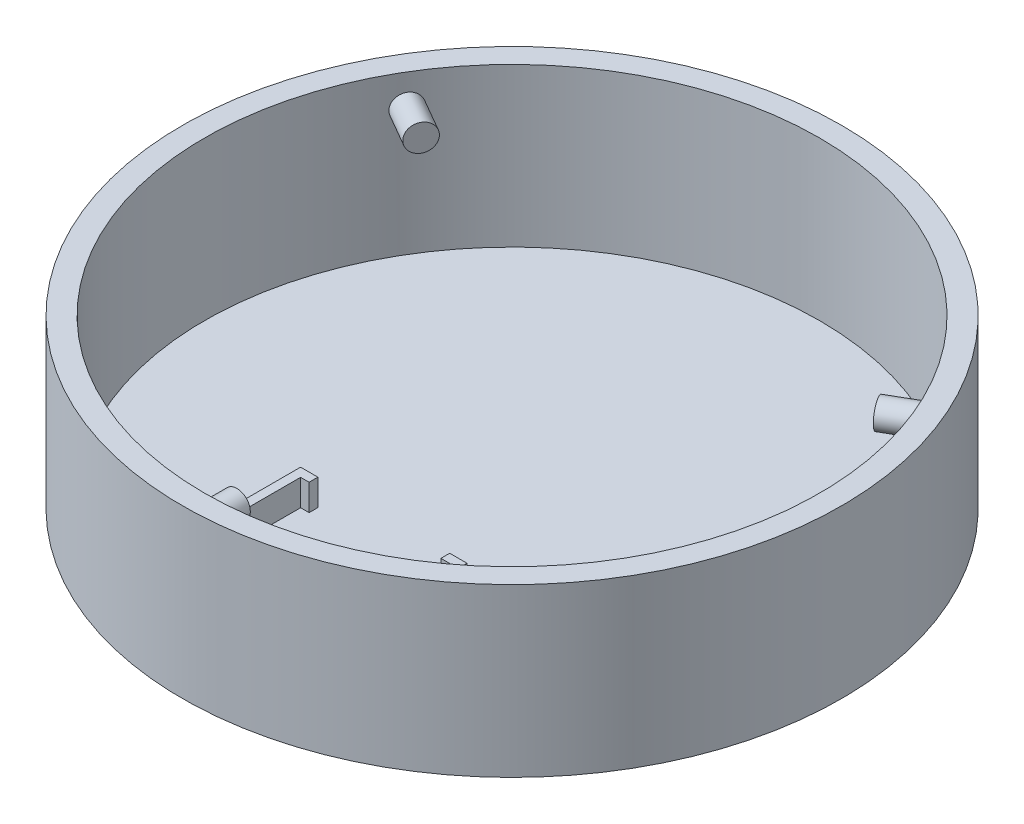
SolidWorks part; units mm, degrees
note: '?' marks a value the reader was unsure of.
ref_plane "Front Plane" through (0, 0, 0) normal (0, 0, 1) x (1, 0, 0)
ref_plane "Top Plane" through (0, 0, 0) normal (0, 1, 0) x (1, 0, 0)
ref_plane "Right Plane" through (0, 0, 0) normal (1, 0, 0) x (0, 0, -1)
sketch "Sketch1" plane through (0, 0, 0) normal (0, 1, 0) x (1, 0, 0)
  circle A0 centre (0, 0) radius 95.25
  dimension "D1" = 190.5
extrude "Boss-Extrude1" add sketch "Sketch1" along normal blind 48.26
sketch "Sketch2" plane through (0, 48.26, 0) normal (0, 1, 0) x (1, 0, 0)
  circle A0 centre (0, 0) radius 88.9
  dimension "D1" = 177.8
extrude "Cut-Extrude1" cut sketch "Sketch2" against normal blind 45.72 contours A0
ref_plane "Plane1" through (0, 0, 88.9) normal (0, 0, -1) x (-1, 0, 0)
sketch "Sketch3" plane through (0, 0, 88.9) normal (0, 0, -1) x (-1, 0, 0)
  line L1 (88.9, 48.26) -> (-88.9, 48.26) construction
  circle A0 centre (1.6268, 39.26) radius 3.875
  dimension "D1" = 7.75
  dimension "D2" = 9
extrude "Boss-Extrude4" add sketch "Sketch3" along normal blind 11 and the other way up to body
ref_axis "Axis1" through (0, 50.673, 0) along (0, -1, 0)?
pattern_circular "CirPattern1" count 3 over 360 about axis through (0, 0, 0) along (0, 1, 0) of "Boss-Extrude4"
sketch "Sketch8" plane through (0, 2.54, 0) normal (0, 1, 0) x (1, 0, 0)
  line L4 (14.8411, -32.9471) -> (-28.1749, -32.9471)
  line L5 (-28.1749, -32.9471) -> (-28.1749, -75.9631)
  line L6 (-28.1749, -75.9631) -> (14.8411, -75.9631)
  line L7 (14.8411, -75.9631) -> (14.8411, -32.9471)
  line L8 (-30.7149, -78.5031) -> (17.3811, -78.5031)
  line L9 (17.3811, -78.5031) -> (17.3811, -30.4071)
  line L10 (17.3811, -30.4071) -> (-30.7149, -30.4071)
  line L11 (-30.7149, -30.4071) -> (-30.7149, -78.5031)
extrude "Boss-Extrude5" add sketch "Sketch8" along normal blind 7.62 contours L11 L8 L9 L10 | L5 L6 L7 L4
sketch "Sketch10" plane through (0, 0, 30.4071) normal (0, 0, -1) x (-1, 0, 0)
  line L0 (-17.3811, 2.54) -> (30.7149, 2.54) construction
  line L1 (-12.3811, 2.54) -> (25.7149, 2.54)
  line L2 (-12.3811, 2.54) -> (-12.3811, 10.16)
  line L3 (-12.3811, 10.16) -> (25.7149, 10.16)
  line L4 (25.7149, 2.54) -> (25.7149, 10.16)
  line L5 (-17.3811, 10.16) -> (30.7149, 10.16) construction
  line L6 (-17.3811, 10.16) -> (-17.3811, 2.54) construction
  line L7 (30.7149, 10.16) -> (30.7149, 2.54) construction
  dimension "D1" = 5
  dimension "D2" = 5
extrude "Cut-Extrude2" cut sketch "Sketch10" against normal up to surface (2.54 mm away) up to face at (-6.6669, 6.35, 32.9471)
